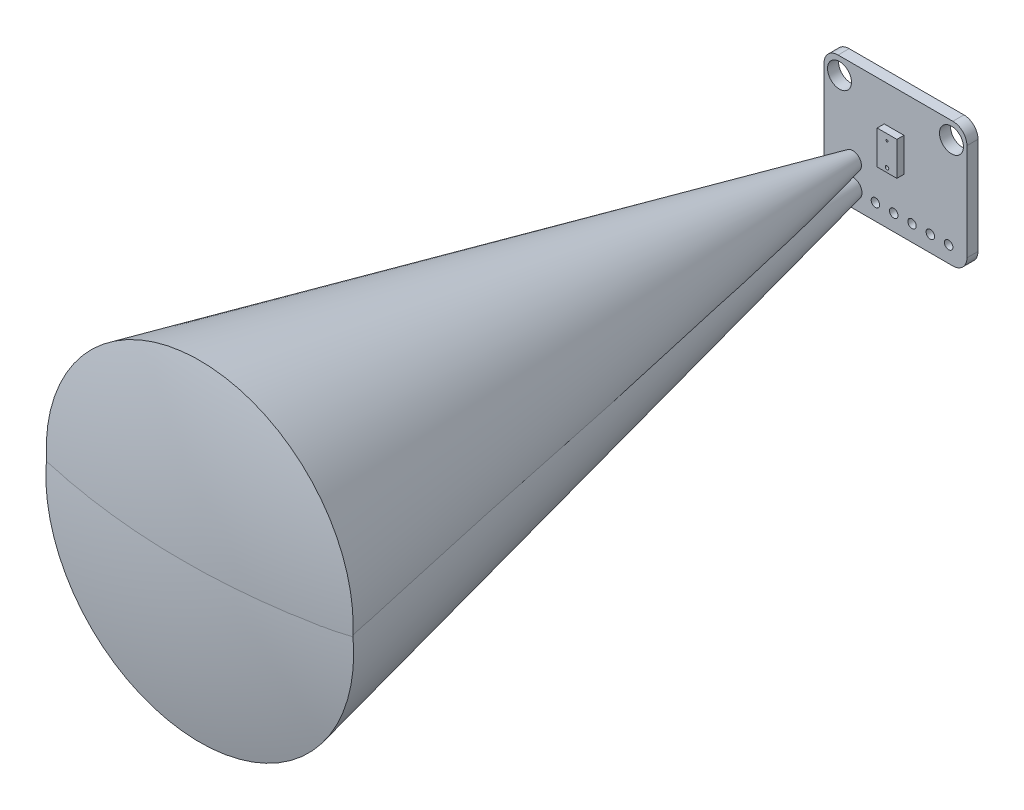
SolidWorks part; units mm, degrees
ref_plane "Front Plane" through (0, 0, 0) normal (0, 0, 1) x (1, 0, 0)
ref_plane "Top Plane" through (0, 0, 0) normal (0, 1, 0) x (1, 0, 0)
ref_plane "Right Plane" through (0, 0, 0) normal (1, 0, 0) x (0, 0, -1)
sketch "Sketch1" plane through (0, 0, 0) normal (0, 0, 1) x (1, 0, 0)
  line L1 (-10.15, -8.9) -> (10.15, -8.9)
  line L2 (-10.15, -8.9) -> (-10.15, 8.9)
  line L3 (-10.15, 8.9) -> (10.15, 8.9)
  line L4 (10.15, -8.9) -> (10.15, 8.9)
  line L5 (-10.15, -8.9) -> (10.15, 8.9) construction
  line L6 (-10.15, 8.9) -> (10.15, -8.9) construction
  point P0 (0, 0)
  dimension "D1" = 20.3
  dimension "D2" = 17.8
extrude "Boss-Extrude1" add sketch "Sketch1" along normal blind 1.57
fillet "Fillet1" radius 2 4 edges at (10.15, -8.9, 0.785) (10.15, 8.9, 0.785) (-10.15, -8.9, 0.785) (-10.15, 8.9, 0.785)
sketch "Sketch2" plane through (0, 0, 1.57) normal (0, 0, 1) x (1, 0, 0)
  line L0 (-10.15, 6.9) -> (-10.15, -6.9) construction
  line L1 (8.15, 8.9) -> (-8.15, 8.9) construction
  line L2 (10.15, -6.9) -> (10.15, 6.9) construction
  line L3 (-8.15, -8.9) -> (8.15, -8.9) construction
  circle A0 centre (-7.95, 6.5) radius 1.7
  circle A1 centre (7.95, 6.5) radius 1.7
  circle A2 centre (-8.05, -6.6) radius 0.6
  circle A3 centre (-5.45, -6.6) radius 0.6
  circle A4 centre (-2.85, -6.6) radius 0.6
  circle A5 centre (-0.25, -6.6) radius 0.6
  circle A6 centre (2.35, -6.6) radius 0.6
  circle A7 centre (4.95, -6.6) radius 0.6
  circle A8 centre (7.55, -6.6) radius 0.6
  dimension "D1" = 3.4
  dimension "D5" = 1.2
  dimension "D2" = 2.2
  dimension "D3" = 2.4
  dimension "D4" = 2.2
  dimension "D6" = 2.3
  dimension "D7" = 2.1
  dimension "D9" = 2.6
  dimension "D8" = 7
extrude "Cut-Extrude1" cut sketch "Sketch2" against normal through all
sketch "Sketch3" plane through (0, 0, 1.57) normal (0, 0, 1) x (1, 0, 0)
  line L0 (-0.2, 2.82) -> (-0.2, -0.5) construction
  line L1 (-1.6, 3.7) -> (1.2, 3.7)
  line L2 (-1.6, 3.7) -> (-1.6, -1.1)
  line L3 (-1.6, -1.1) -> (1.2, -1.1)
  line L4 (1.2, 3.7) -> (1.2, -1.1)
  line L5 (8.15, 8.9) -> (-8.15, 8.9) construction
  line L6 (-10.15, 6.9) -> (-10.15, -6.9) construction
  circle A0 centre (-0.2, -0.5) radius 0.25
  circle A1 centre (-0.2, 2.82) radius 0.15
  point P4 (-0.21, 1.3566)
  dimension "D4" = 0.6
  dimension "Position Return Aperture" = 0.3
  dimension "LIGHT EMISSION APERTURE" = 0.5
  dimension "D5" = 3.32
  dimension "D1" = 4.8
  dimension "D2" = 2.8
  dimension "D3" = 1.4
  dimension "D6" = 5.2
  dimension "D7" = 8.55
extrude "Boss-Extrude2" add sketch "Sketch3" along normal blind 1
ref_axis "Proximity Sensor View Cone" through (-0.2, 2.82, 15.2359) along (0, 0, -1)
ref_plane "Plane1" through (0, 2.82, 0) normal (0, 1, 0) x (1, 0, 0)
sketch "Sketch4" plane through (0, 2.82, 0) normal (0, 1, 0) x (1, 0, 0)
  line L0 (-0.2, -1.86) -> (-21.9976, -100.1828)
  line L1 (-0.2, -1.86) -> (21.5976, -100.1828)
  line L2 (-0.2, -2.57) -> (-0.2, -1.86) construction
  line L3 (-0.35, -2.57) -> (-0.05, -2.57) construction
  line L4 (1.2, -2.57) -> (-1.6, -2.57) construction
  line L5 (-0.3574, -2.57) -> (-0.0426, -2.57) construction
  line L7 (-0.2, -1.86) -> (-0.2, -102.57)
  arc A0 (-21.9976, -100.1828) -> (21.5976, -100.1828) centre (-0.2, -1.86) ccw
  arc A1 (-1.4359, -7.4347) -> (1.0359, -7.4347) centre (-0.2, -1.86) ccw
  point P9 (-0.2, -102.57)
  point P12 (-0.2, -2.57)
  point P14 (-0.2, -7.57)
  dimension "D1" = 0.71
  dimension "D2" = 25
  dimension "D3" = 100
  dimension "D4" = 5
revolve "Revolve1" add sketch "Sketch4" angle 360 about L7 region at (7.117, 2.82, 68.6713)
ref_axis "Proximity Sensor Illumination Cone" through (-0.2, -0.5, 18.5008) along (0, 0, -1)
ref_plane "Plane2" through (0, -0.5, 0) normal (0, 1, 0) x (1, 0, 0)
sketch "Sketch5" plane through (0, -0.5, 0) normal (0, 1, 0) x (1, 0, 0)
  line L0 (-0.2, -1.57) -> (-0.2, -102.57)
  line L1 (-0.45, -1.57) -> (0.05, -1.57) construction
  line L2 (-0.2, -1.57) -> (-22.0604, -100.1759)
  line L3 (-0.2, -1.57) -> (21.6604, -100.1759)
  line L4 (-0.2, -2.57) -> (-0.4217, -2.57) construction
  line L5 (-0.45, -2.57) -> (0.05, -2.57) construction
  line L6 (-0.2, -2.57) -> (0.0217, -2.57) construction
  line L7 (-1.6, -2.57) -> (1.2, -2.57) construction
  arc A0 (-22.0604, -100.1759) -> (21.6604, -100.1759) centre (-0.2, -1.57) ccw
  arc A1 (-1.4986, -7.4278) -> (1.0986, -7.4278) centre (-0.2, -1.57) ccw
  point P4 (-0.2, -7.57)
  dimension "D1" = 25
  dimension "D2" = 100
  dimension "D3" = 5
revolve "Revolve2" add sketch "Sketch5" angle 360 about axis through (-0.2, -0.5, 18.5008) along (0, 0, -1) region at (7.1402, -0.5, 68.593)
